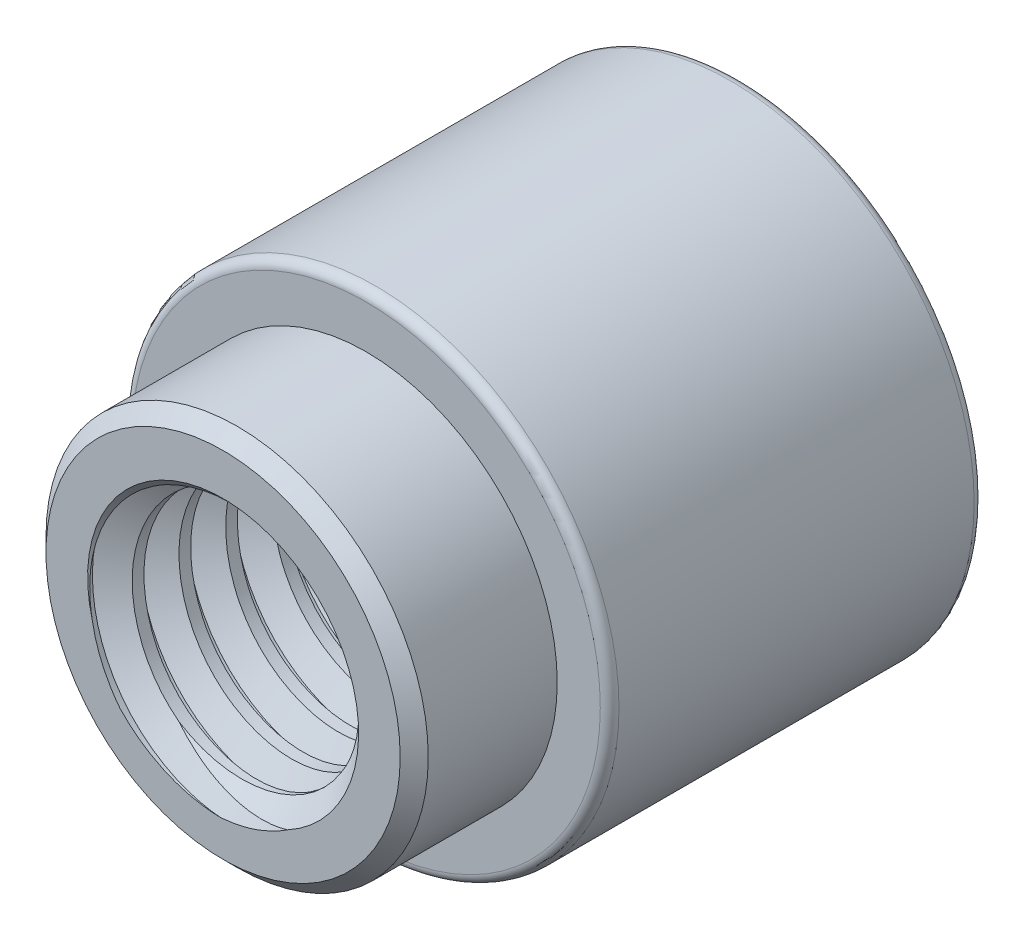
SolidWorks part; units mm, degrees
ref_plane "Ebene vorne" through (0, 0, 0) normal (0, 0, 1) x (1, 0, 0)
ref_plane "Ebene oben" through (0, 0, 0) normal (0, 1, 0) x (1, 0, 0)
ref_plane "Ebene rechts" through (0, 0, 0) normal (1, 0, 0) x (0, 0, -1)
sketch "Skizze1" plane through (0, 0, 0) normal (1, 0, 0) x (0, 0, -1)
  line L0 (-1.38, 2.045) -> (-1.53, 1.895)
  line L1 (0, 1.25) -> (-1.53, 1.25)
  line L2 (-1.53, 1.895) -> (-1.53, 1.25)
  line L3 (-1.38, 2.045) -> (0, 2.045)
  line L4 (0, 2.045) -> (0, 2.5058)
  line L5 (0.1, 2.6058) -> (3.9, 2.6058)
  line L6 (4, 2.5058) -> (4, 1.25)
  line L7 (4, 1.25) -> (0, 1.25)
  line L8 (-1.53, 0) -> (3, 0)
  arc A0 (0, 2.5058) -> (0.1, 2.6058) centre (0.1, 2.5058) cw
  arc A1 (3.9, 2.6058) -> (4, 2.5058) centre (3.9, 2.5058) cw
  point P5 (-1.53, 2.045)
  point P10 (0, 2.6058)
  point P13 (4, 2.6058)
  dimension "D5" = 0.1
  dimension "D1" = 1.25
  dimension "D2" = 2.045
  dimension "D3" = 1.53
  dimension "D4" = 4
revolve "Rotation1" add sketch "Skizze1" angle 360 about L8 region at (0, 1.8759, -1.4982)
thread "Gewinde1" pitch 0.5 method cut profile "Gewindeprofil1" start angle 0, offset 1, length 0, pitch 0.5, diameter 2.5
ref_plane "Ebene1" through (1.25, 0, -5) normal (0, -1, 0) x (1, 0, 0)
sketch "Gewindeprofil1" plane through (1.25, 0, -5) normal (0, -1, 0) x (1, 0, 0)
  line L0 (0, 0) -> (0, 0.5) construction
  line L1 (0, 0) -> (0.2706, 0.1562)
  line L2 (0.2706, 0.1562) -> (0.2706, 0.2187)
  line L3 (0.2706, 0.2187) -> (0, 0.375)
  line L4 (0.2706, 0.1875) -> (0, 0.1875) construction
  line L11 (0, 0) -> (0, 0.375)
  point P2 (0, 0)
  dimension "Pitch" = 0.5
  dimension "Profile_Angle" = 60
  dimension "Profile_Land" = 0.0625
  dimension "Profile_Height" = 0.2706
sketch "Skizze4" plane through (0, 0, 0) normal (1, 0, 0) x (0, 0, -1)
  line L0 (-1.53, 1.25) -> (-1.33, 1.25)
  line L1 (0, 1.25) -> (-1.53, 1.25) construction
  line L2 (-1.53, 1.25) -> (-1.53, 1.45)
  line L3 (-1.53, 1.45) -> (-1.33, 1.25)
  line L4 (4, 1.25) -> (2.8, 1.25)
  line L5 (2.8, 1.25) -> (4, 1.45)
  line L6 (4, 2.5058) -> (4, 1.25) construction
  line L7 (4, 1.45) -> (4, 1.25)
  line L8 (-1.53, 0) -> (3, 0)
revolve "Schnitt-Rotation1" cut sketch "Skizze4" angle 360 about L8 region at (0, 1.3167, 1.4633) region at (0, 1.3167, -3.6)
